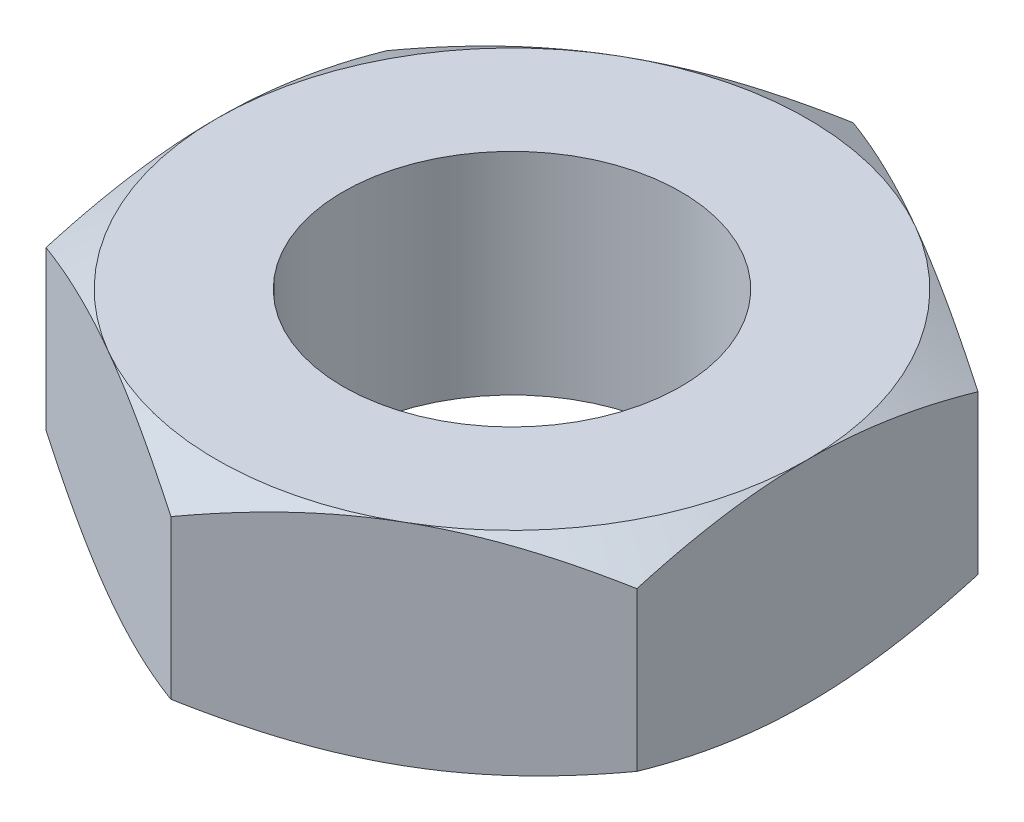
SolidWorks part; units mm, degrees
ref_plane "Front Plane" through (0, 0, 0) normal (0, 0, 1) x (1, 0, 0)
ref_plane "Top Plane" through (0, 0, 0) normal (0, 1, 0) x (1, 0, 0)
ref_plane "Right Plane" through (0, 0, 0) normal (1, 0, 0) x (0, 0, -1)
sketch "Sketch1" plane through (0, 0, 0) normal (0, 1, 0) x (1, 0, 0)
  line L1 (-5.5563, 3.2079) -> (-5.5563, -3.2079)
  line L2 (-5.5563, -3.2079) -> (0, -6.4158)
  line L3 (0, -6.4158) -> (5.5562, -3.2079)
  line L4 (5.5562, -3.2079) -> (5.5562, 3.2079)
  line L5 (5.5562, 3.2079) -> (0, 6.4158)
  line L6 (0, 6.4158) -> (-5.5563, 3.2079)
  circle A0 centre (0, 0) radius 5.5563 construction
  circle A1 centre (0, 0) radius 3.175
  dimension "Thread Size" = 6.35
  dimension "Hex" = 11.1125
extrude "Boss-Extrude1" add sketch "Sketch1" along normal mid plane 3.9688
sketch "Sketch2" plane through (0, 1.9844, 0) normal (0, 1, 0) x (1, 0, 0)
  circle A0 centre (0, 0) radius 3.175 construction
  circle A1 centre (0, 0) radius 3.175
curve "Helix/Spiral1" pitch 0.9071 height 4.8759 turns 5.375 parameters "Pitch"=0.9071
sketch "Sketch3" plane through (0, 0, 0) normal (1, 0, 0) x (0, 0, -1)
  line L0 (2.5858, 2.4379) -> (3.175, 2.7781)
  line L1 (3.175, 2.7781) -> (3.175, 1.9844)
  line L2 (3.175, 1.9844) -> (2.5858, 2.3246)
  line L3 (2.5858, 2.3246) -> (2.5858, 2.4379)
  line L4 (2.8804, 2.608) -> (2.8804, 2.1545) construction
  line L5 (2.5858, 2.3812) -> (3.175, 2.3812) construction
  line L6 (3.175, 1.9844) -> (-3.175, 1.9844) construction
  dimension "D1" = 60
  dimension "D2" = 0.1134
  dimension "D3" = 0.4536
sweep "Sweep1" [suppressed] add profiles "Sketch3" path "Helix/Spiral1"
sketch "Sketch4" plane through (0, 1.9844, 0) normal (0, 1, 0) x (1, 0, 0)
  circle A1 centre (0, 0) radius 3.175
  circle A2 centre (0, 0) radius 3.175
  dimension "D1" = 0
extrude "Cut-Extrude1" [suppressed] cut sketch "Sketch4" along normal through all and the other way through all draft 45
sketch "Sketch5" plane through (0, 1.9844, 0) normal (0, 1, 0) x (1, 0, 0)
  circle A0 centre (0, 0) radius 5.5563 construction
  circle A1 centre (0, 0) radius 5.5563
extrude "Cut-Extrude2" cut sketch "Sketch5" against normal through all draft 60 flip side to cut
mirror "Mirror1" about plane through (0, 0, 0) normal (0, 1, 0) of "Cut-Extrude2", "Cut-Extrude1"
equation "\"D2@Sketch3\" = \"Pitch@Helix/Spiral1\"*.125"
equation "\"D3@Sketch3\" = \"Pitch@Helix/Spiral1\"*.5"
equation "\"D3@Helix/Spiral1\" = \"Height@Boss-Extrude1\"+\"Pitch@Helix/Spiral1\""
